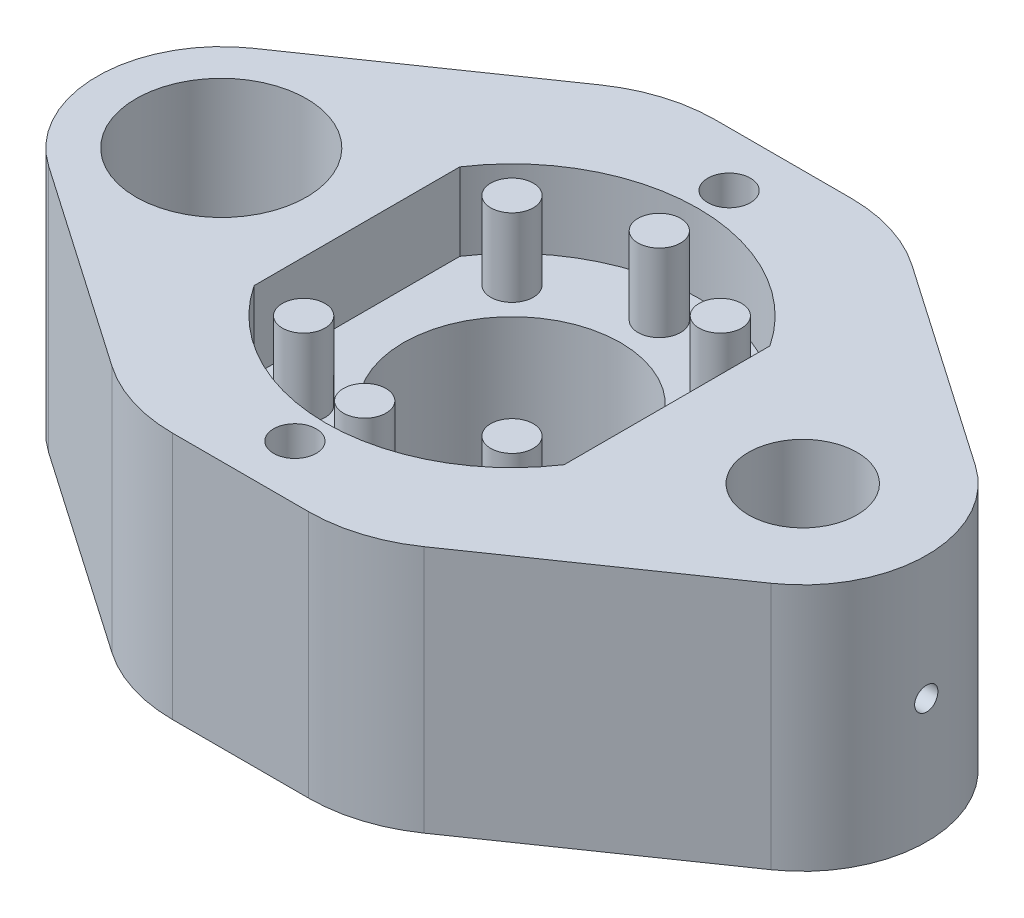
SolidWorks part; units mm, degrees
ref_plane "Front Plane" through (0, 0, 0) normal (0, 0, 1) x (1, 0, 0)
ref_plane "Top Plane" through (0, 0, 0) normal (0, 1, 0) x (1, 0, 0)
ref_plane "Right Plane" through (0, 0, 0) normal (1, 0, 0) x (0, 0, -1)
sketch "Sketch1" plane through (0, 0, 0) normal (0, 1, 0) x (1, 0, 0)
  line L0 (-20, 13.2665) -> (-20, -13.2665)
  line L1 (20, 13.2665) -> (20, -13.2665)
  line L2 (-15, -35) -> (15, -35)
  line L3 (-15, -35) -> (-46.5969, -13.1623)
  line L4 (0, 105.5868) -> (0, -105.5868) construction
  line L5 (15, -35) -> (46.5969, -13.1623)
  line L6 (-86.2788, 0) -> (86.2788, 0) construction
  line L7 (-15, 35) -> (15, 35)
  line L8 (15, 35) -> (46.5969, 13.1623)
  line L9 (-15, 35) -> (-46.5969, 13.1623)
  circle A0 centre (0, 0) radius 14
  arc A1 (-20, -13.2665) -> (20, -13.2665) centre (0, 0) ccw
  arc A2 (20, 13.2665) -> (-20, 13.2665) centre (0, 0) ccw
  arc A3 (-46.5969, 13.1623) -> (-46.5969, -13.1623) centre (-37.5, 0) ccw
  circle A4 centre (-37.5, 0) radius 11
  circle A5 centre (37.5, 0) radius 7
  arc A6 (46.5969, 13.1623) -> (46.5969, -13.1623) centre (37.5, 0) cw
  point P13 (0, -35)
  point P16 (0, 0)
  point P24 (0, 0)
  dimension "D1" = 28
  dimension "D2" = 48
  dimension "D4" = 22
  dimension "D5" = 32
  dimension "D9" = 14
  dimension "D3" = 40
  dimension "D6" = 37.5
  dimension "D7" = 30
  dimension "D8" = 35
extrude "Extrude2" add sketch "Sketch1" along normal blind 32 contours A6 L8 L7 L9 A3 L3 L2 L5 A2 L1 A1 L0 A4 region at (-30.0715, 0, 23.0293)
extrude "Extrude3" add sketch "Sketch" along normal offset from surface (22 mm away) 10 contours L1 A2 L0 A1 A0 region at (0, 0, -23.3752) up to face at (0, 32, 0)
sketch "Sketch" plane through (0, 0, 0) normal (0, 1, 0) x (1, 0, 0) same geometry as "Sketch1"
fillet "Fillet1" radius 20 4 edges at (-15, 16, -35) (15, 16, -35) (15, 16, 35) (-15, 16, 35)
sketch "Sketch5" plane through (0, 22, 0) normal (0, 1, 0) x (1, 0, 0)
  circle A0 centre (13.435, 13.435) radius 2.75
  dimension "D1" = 5.5
extrude "Extrude5" add sketch "Sketch5" along normal up to surface (10 mm away) up to face at (0, 32, 0)
pattern_circular "CirPattern1" count 3 every 45 about axis through (0, 22, 0) along (0, 1, 0) of "Extrude5"
mirror "Mirror1" about plane through (0, 0, 0) normal (0, 0, 1) of "Extrude5", "CirPattern1"
sketch3d "3DSketch3"
  circle A0 centre (37.5, 16, 0) radius 8
  circle A1 centre (37.5, 16, 0) radius 1.5
  circle A2 centre (37.5, 32, 0) radius 7 construction
  point P3 (37.5, 39, 0)
  point P5 (39, 16, 0)
  point P7 (37.5, 24, 0)
  dimension "D1" = 16
  dimension "D2" = 16
  dimension "D3" = 3
extrude "Extrude10" cut sketch "3DSketch3" along direction (0, 1, 0) on the side against the normal mid plane 3 contours A0
extrude "Extrude11" cut sketch "Sketch" along direction (1, 0, 0) on the side of the normal through all contours A1
sketch3d "Sketch" same geometry as "3DSketch3"
hole_wizard "M5 Clearance Hole1" positions "Sketch6" profile "Sketch7" hole size "M5" standard "ISO" end condition through all
sketch "Sketch6" plane through (0, 32, 0) normal (0, 1, 0) x (1, 0, 0)
  point P0 (0, 28)
  point P3 (0, -28)
sketch "Sketch7" plane through (0, 32, -28) normal (1, 0, 0) x (0, 0, 1)
  line L0 (0, 0) -> (0, 32)
  line L1 (0, 32) -> (2.75, 32)
  line L2 (2.75, 32) -> (2.75, 0)
  line L5 (2.75, 0) -> (0, 0)
  line L11 (0, -6.35) -> (0, 107.95) construction
  dimension "Thru Hole Dia." = 5.5
  dimension "Thru Hole Depth" = 32
